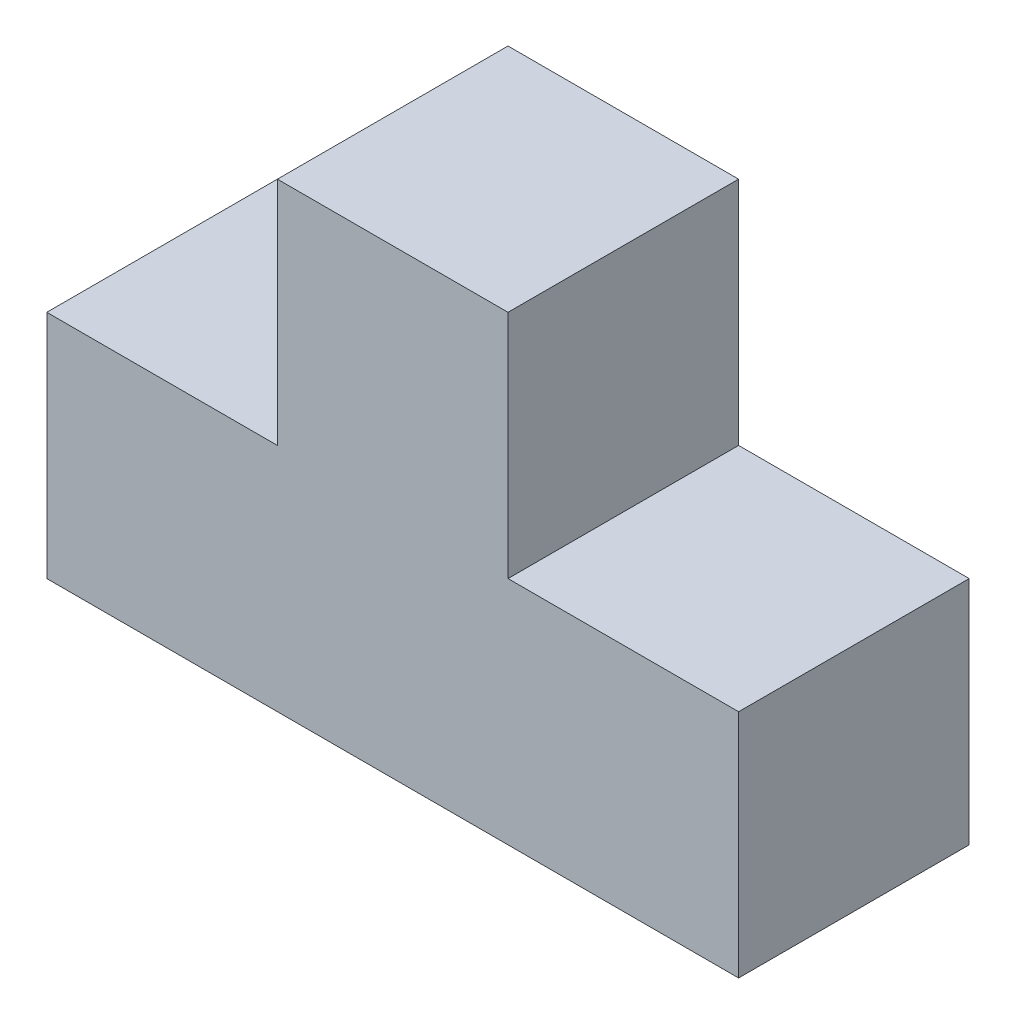
SolidWorks part; units mm, degrees
ref_plane "前基準面" through (0, 0, 0) normal (0, 0, 1) x (1, 0, 0)
ref_plane "上基準面" through (0, 0, 0) normal (0, 1, 0) x (1, 0, 0)
ref_plane "右基準面" through (0, 0, 0) normal (1, 0, 0) x (0, 0, -1)
ref_plane "平面1"
sketch "草圖1" plane through (0, 0, 0) normal (0, 0, 1) x (1, 0, 0)
  line L0 (-45, 0) -> (45, 0)
  line L1 (45, 0) -> (45, 30)
  line L2 (45, 30) -> (15, 30)
  line L3 (15, 30) -> (15, 60)
  line L4 (15, 60) -> (-15, 60)
  line L5 (-15, 60) -> (-15, 30)
  line L6 (-15, 30) -> (-45, 30)
  line L7 (-45, 30) -> (-45, 0)
  dimension "D1" = 90
  dimension "D2" = 30
  dimension "D3" = 30
  dimension "D4" = 30
  dimension "D5" = 30
  dimension "D6" = 30
  dimension "D7" = 30
extrude "擠出1" add sketch "草圖1" along normal blind 15 and the other way blind 15
